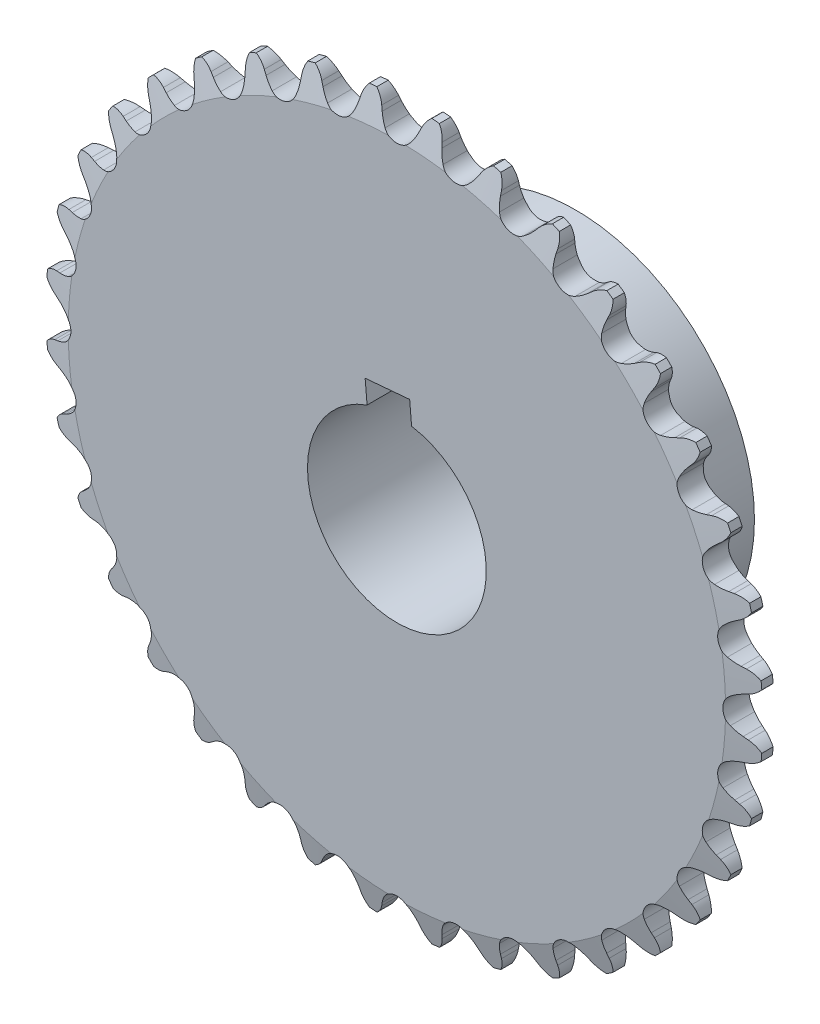
SolidWorks part; units mm, degrees
ref_plane "Front Plane" through (0, 0, 0) normal (0, 0, 1) x (1, 0, 0)
ref_plane "Top Plane" through (0, 0, 0) normal (0, 1, 0) x (1, 0, 0)
ref_plane "Right Plane" through (0, 0, 0) normal (1, 0, 0) x (0, 0, -1)
ref_axis "Axis1" through (0, 0, -88.99) along (0, 0, 1)
sketch "Sprocket-BaseSketch" plane through (0, 0, 0) normal (1, 0, 0) x (0, 0, -1)
  line L0 (1.397, 0) -> (1.397, 35.0204)
  line L1 (1.397, 35.0204) -> (0.6032, 38.1954)
  line L2 (0.6032, 38.1954) -> (-0.6032, 38.1954)
  line L3 (-0.6032, 38.1954) -> (-1.397, 35.0204)
  line L4 (-1.397, 35.0204) -> (-1.397, 0)
  line L5 (-1.397, 0) -> (1.397, 0)
  line L6 (5.588, 0) -> (-1.7463, 0) construction
  dimension "Hub Surface" = 1.397
  dimension "RightSide (1)" = 0.7938
  dimension "RightSide (2)" = 3.175
  dimension "OD" = 38.1954
  dimension "LeftSide (1)" = 0.7938
  dimension "LeftSide (2)" = 3.175
  dimension "Tooth Width" = 2.794
revolve "25 (04C) ANSI (ISO) Chain Number, 2.868in P.D." add sketch "Sprocket-BaseSketch" angle 360 about L6
sketch "Tooth-Sketch" plane through (0, 0, 0) normal (0, 0, 1) x (1, 0, 0)
  line L0 (0, 0) -> (0, 48.5721) construction
  line L1 (1.9526, 36.5067) -> (2.1137, 36.9439)
  line L2 (-1.9526, 36.5067) -> (-2.1137, 36.9439)
  line L3 (0, 36.429) -> (6.3258, 35.8756) construction
  line L4 (0, 36.429) -> (-6.3258, 35.8756) construction
  arc A0 (-1.3615, 35.4154) -> (1.3615, 35.4154) centre (0, 36.429) ccw
  arc A1 (1.3615, 35.4154) -> (1.9526, 36.5067) centre (-2.1189, 38.0065) ccw
  arc A2 (-1.3615, 35.4154) -> (-1.9526, 36.5067) centre (2.1189, 38.0065) cw
  arc A3 (2.1137, 36.9439) -> (4.6052, 38.6813) centre (4.6052, 36.0261) cw
  arc A4 (-2.1137, 36.9439) -> (-4.6052, 38.6813) centre (-4.6052, 36.0261) ccw
  arc A5 (4.6052, 38.6813) -> (-4.6052, 38.6813) centre (0, 0) ccw
extrude "Tooth-Cut, Number of teeth: 36" cut sketch "Tooth-Sketch" against normal through all and the other way through all
pattern_circular "Tooth Pattern, 36 / 36" count 36 every 10 about axis through (0, 0, -88.99) along (0, 0, 1) of "Tooth-Cut, Number of teeth: 36"
sketch "Sketch3" plane through (0, 0, 0) normal (1, 0, 0) x (0, 0, -1)
  line L0 (-16.256, 0) -> (16.256, 0) construction
  line L1 (1.397, 0) -> (1.397, 19.05)
  line L2 (1.397, 19.05) -> (17.653, 19.05)
  line L3 (17.653, 19.05) -> (17.653, 0)
  line L4 (17.653, 0) -> (1.397, 0)
  dimension "Hub Mounting" = 1.397
  dimension "Hub OD" = 19.05
  dimension "Hub Width" = 16.256
revolve "Hub-Revolve1" add sketch "Sketch3" angle 360 about L0
sketch "Sketch4" plane through (0, 0, -17.653) normal (0, 0, -1) x (-1, 0, 0)
  circle A0 centre (0, 0) radius 9.525
  dimension "Bore Diameter " = 19.05
extrude "Cut-Extrude1" cut sketch "Sketch4" against normal through all
sketch "Sketch5" plane through (0, 0, 0) normal (1, 0, 0) x (0, 0, -1)
  line L0 (17.653, 0) -> (-1.397, 0) construction
  line L1 (17.653, -19.05) -> (17.653, 19.05) construction
  line L2 (-1.397, 0.9284) -> (-1.397, -0.9284) construction
ref_plane "Plane1" through (0, 0, 0) normal (-0.0872, 0.9962, 0) x (-0.9962, -0.0872, 0)
sketch "Sketch6" plane through (0, 0, -17.653) normal (0, 0, -1) x (-1, 0, 0)
  line L0 (-1.5684, 9.395) -> (-1.3609, 11.7672)
  line L1 (-1.3609, 11.7672) -> (3.3835, 11.3521)
  line L2 (3.3835, 11.3521) -> (3.176, 8.9799)
  line L3 (3.176, 8.9799) -> (-1.5684, 9.395)
  line L4 (10.4376, -0.9132) -> (-10.4376, 0.9132) construction
  circle A0 centre (0, 0) radius 9.525 construction
  dimension "Keyway Wd " = 4.7625
  dimension "Keyway Dp " = 2.3813
extrude "Cut-Extrude2" cut sketch "Sketch6" against normal through all
sketch "Sketch7" plane through (-1.0113, 11.5596, 0) normal (0.0872, -0.9962, 0) x (0.9962, 0.0872, 0)
  line L0 (0, -17.653) -> (0, -1.397) construction
  line L1 (-2.3813, -17.653) -> (2.3812, -17.653) construction
  line L2 (-2.1263, -1.397) -> (2.1263, -1.397) construction
  line L3 (-2.3813, 1.397) -> (-2.3813, -17.653) construction
  circle A0 centre (0, -9.525) radius 2.3813
extrude "Cut-Extrude3" cut sketch "Sketch7" against normal through all draft 1 draft outward yes
sketch "Sketch8" plane through (-1.0113, 11.5596, 0) normal (0.0872, -0.9962, 0) x (0.9962, 0.0872, 0)
  line L0 (-2.3813, -9.525) -> (-2.5083, -9.525) construction
  line L1 (-2.3813, 1.397) -> (-2.3813, -17.653) construction
  line L2 (-2.4448, -9.525) -> (-2.4448, -17.653) construction
  line L3 (-19.05, -17.653) -> (19.05, -17.653) construction
  circle A0 centre (0, -9.525) radius 2.4448
  arc A1 (-2.3813, -9.525) -> (2.3812, -9.525) centre (0, -9.525) ccw construction
  arc A2 (2.3812, -9.525) -> (-2.3813, -9.525) centre (0, -9.525) ccw construction
  spline S0 degree 3 poles (-1.9557, -11.132) (-1.5932, -11.4717) (-1.4632, -11.5712) (-1.1858, -11.7439) (-1.0365, -11.8177) (-0.7286, -11.9336) (-0.5706, -11.9759) (-0.2467, -12.0294) (-0.0797, -12.0403) (0.2479, -12.0293) (0.4102, -12.0079) (0.732, -11.9326) (0.8885, -11.8791) (1.1861, -11.7438) (1.3295, -11.6609) (1.5971, -11.4684) (1.7198, -11.3604) (1.9432, -11.1214) (2.0447, -10.9888) (2.2174, -10.7103) (2.2896, -10.5637) (2.4054, -10.2557) (2.4484, -10.0947) (2.5015, -9.7718) (2.5124, -9.6081) (2.5015, -9.2764) (2.4799, -9.1138) (2.4056, -8.7951) (2.3521, -8.6372) (2.2164, -8.3377) (2.1347, -8.1962) (1.9439, -7.9294) (1.8339, -7.804) (1.5954, -7.5803) (1.4659, -7.4806) (1.1858, -7.3059) (1.0376, -7.2328) (0.7317, -7.1174) (0.5718, -7.0743) (0.2459, -7.0204) (0.0825, -7.0098) (-0.2452, -7.0204) (-0.411, -7.0423) (-0.7306, -7.1171) (-0.8855, -7.1697) (-1.1852, -7.3057) (-1.3291, -7.389) (-1.5946, -7.5796) (-1.718, -7.6878) (-1.944, -7.9294) (-2.0434, -8.0594) (-2.2159, -8.337) (-2.2897, -8.4865) (-2.4054, -8.7942) (-2.4477, -8.9522) (-2.5014, -9.2762) (-2.5123, -9.4431) (-2.4963, -9.9344) (-2.4198, -10.2626) (-2.1505, -10.8584) (-1.9557, -11.132) (-1.5932, -11.4717) (-1.4632, -11.5712) knots -0.0625 -0.0625 0 0 0.03125 0.03125 0.0625 0.0625 0.09375 0.09375 0.125 0.125 0.15625 0.15625 0.1875 0.1875 0.21875 0.21875 0.25 0.25 0.28125 0.28125 0.3125 0.3125 0.34375 0.34375 0.375 0.375 0.40625 0.40625 0.4375 0.4375 0.46875 0.46875 0.5 0.5 0.53125 0.53125 0.5625 0.5625 0.59375 0.59375 0.625 0.625 0.65625 0.65625 0.6875 0.6875 0.71875 0.71875 0.75 0.75 0.78125 0.78125 0.8125 0.8125 0.84375 0.84375 0.875 0.875 0.9375 0.9375 1 1 1.03125 1.03125 1.0625 only from (-1.714, -11.3585) to (-1.714, -11.3585) construction
extrude "Extrude1" add sketch "Sketch8" against normal up to surface (7.2887 mm away) up to face at (-0.3888, 19.046, -7.361)
sketch "Sketch9" plane through (-1.0113, 11.5596, 0) normal (0.0872, -0.9962, 0) x (0.9962, 0.0872, 0)
  line L0 (0, -9.525) -> (2.4448, -9.525) construction
  line L1 (1.2224, -9.525) -> (1.2224, -11.6422) construction
  line L3 (0, -10.9365) -> (1.2224, -10.2307)
  line L4 (1.2224, -10.2307) -> (1.2224, -8.8193)
  line L5 (1.2224, -8.8193) -> (0, -8.1135)
  line L6 (0, -8.1135) -> (-1.2224, -8.8193)
  line L7 (-1.2224, -8.8193) -> (-1.2224, -10.2307)
  line L8 (-1.2224, -10.2307) -> (0, -10.9365)
  circle A0 centre (0, -9.525) radius 2.4448 construction
  circle A1 centre (0, -9.525) radius 1.2224 construction
extrude "Cut-Extrude4" cut sketch "Sketch9" against normal through all from offset 2.54 offset against normal yes
pattern_circular "CirPattern1" count 2 over 90 about axis through (0, 0, 16.256) along (0, 0, -1) of "Cut-Extrude3", "Extrude1", "Cut-Extrude4"
sketch "Sketch10" plane through (0, 0, -17.653) normal (0, 0, -1) x (-1, 0, 0)
  line L0 (-38.0501, 3.3289) -> (38.0501, -3.3289)
  line L1 (-6.3258, -35.8756) -> (0, -36.429)
  line L2 (10.4376, -0.9132) -> (-10.4376, 0.9132) construction
  line L3 (-38.2797, 0.7037) -> (37.8204, -5.9542)
  line L4 (-6.0962, -33.2504) -> (0.2297, -33.8038)
  circle A0 centre (0, 0) radius 38.1954
  circle A1 centre (0, 0) radius 9.525
  arc A2 (-1.5684, 9.395) -> (3.176, 8.9799) centre (0, 0) ccw construction
  arc A3 (27.2924, 26.7211) -> (26.7211, 27.2924) centre (0, 0) ccw construction
  dimension "D1" = 2.6353
  dimension "D2" = 2.6353
equation "\"D1@Sketch10\" = \"D2@Sketch10\""
